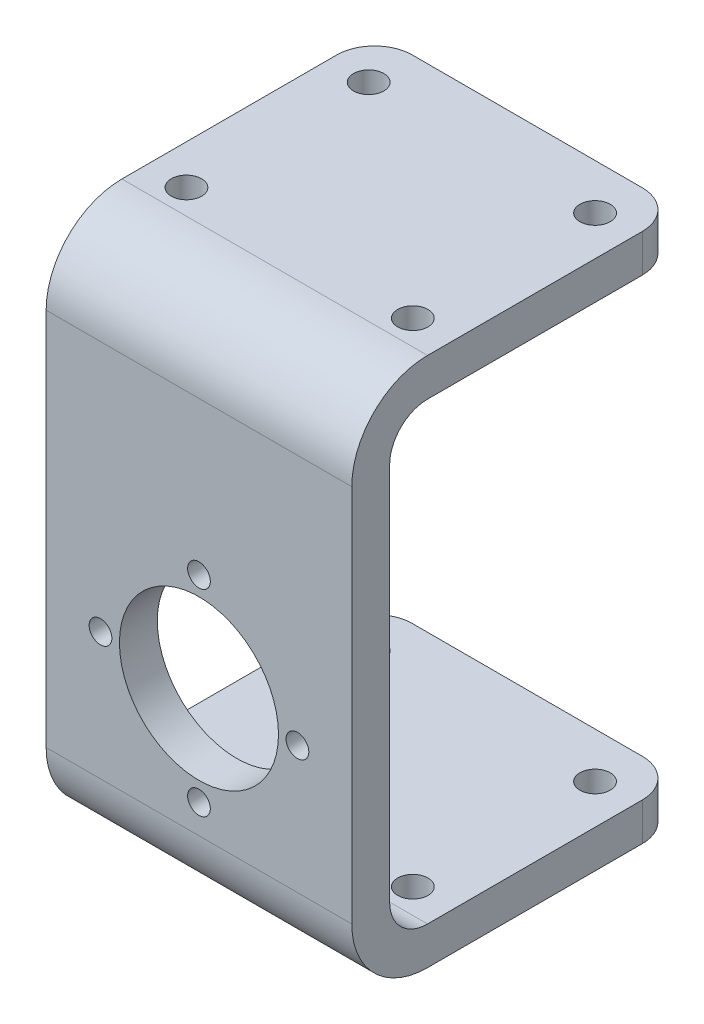
SolidWorks part; units mm, degrees
material "Acrylic"
ref_plane "Front Plane" through (0, 0, 0) normal (0, 0, 1) x (1, 0, 0)
ref_plane "Top Plane" through (0, 0, 0) normal (0, 1, 0) x (1, 0, 0)
ref_plane "Right Plane" through (0, 0, 0) normal (1, 0, 0) x (0, 0, -1)
sketch "Sketch1" plane through (0, 0, 0) normal (0, 1, 0) x (1, 0, 0)
  line L1 (-47.1412, -7.433) -> (-6.7912, -7.433)
  line L2 (-47.1412, -7.433) -> (-47.1412, -50.783)
  line L3 (-47.1412, -50.783) -> (-6.7912, -50.783)
  line L4 (-6.7912, -7.433) -> (-6.7912, -50.783)
extrude "Boss-Extrude1" add sketch "Sketch1" along normal blind 47
sketch "Sketch3" plane through (0, 0, 50.783) normal (0, 0, 1) x (1, 0, 0)
  line L6 (-47.1412, 26.825) -> (-47.1412, 47)
  line L7 (-47.1412, 47) -> (-6.7912, 47)
  line L8 (-6.7912, 26.825) -> (-6.7912, 47)
  arc A1 (-6.7912, 26.825) -> (-47.1412, 26.825) centre (-26.9662, 26.825) ccw
  line M2 (-6.7912, 0) -> (-6.7912, 47)
  line M3 (-6.7912, 47) -> (-47.1412, 47)
  line M4 (-47.1412, 47) -> (-47.1412, 0)
extrude "Cut-Extrude2" cut sketch "Sketch3" against normal blind 102 contours A1 L7 M4 | A1 M2 M3 region at (-11.2977, 42.4936, 50.783) region at (-42.6348, 42.4936, 50.783)
fillet "Fillet1" radius 10 1 edges at (-26.9662, 0, 50.783)
sketch "Sketch5" plane through (-47.1412, 0, 0) normal (-1, 0, 0) x (0, 0, 1)
  line L0 (7.433, 0) -> (-6.6658, 0)
  line L1 (-6.6658, 0) -> (-6.6658, 5)
  line L2 (50.783, 47) -> (50.783, 59.7784)
  line L3 (50.783, 59.7784) -> (45.783, 59.7784)
  line L5 (-6.6658, 5) -> (36.5956, 5)
  line L6 (-6.6658, 5) -> (-6.6658, 59.7784)
  line L7 (-6.6658, 59.7784) -> (45.783, 59.7784)
  line L8 (45.783, 17.5785) -> (45.783, 59.7784)
  line L9 (36.5956, 5) -> (40.783, 5)
  line L12 (45.783, 10) -> (45.783, 17.5785)
  arc A1 (40.783, 5) -> (45.783, 10) centre (40.783, 10) ccw
  line M2 (50.783, 26.825) -> (7.433, 26.825)
  line M3 (7.433, 26.825) -> (7.433, 0)
  dimension "D1" = 5
  dimension "D2" = 5
extrude "Cut-Extrude3" cut sketch "Sketch5" against normal blind 102 contours L8 L7 L6 L5 M2 M3 | L5 L8 M2 M3 region at (-47.1412, 15.9757, 26.4915) region at (-47.1412, 39.1625, 16.6608)
fillet "Fillet2" radius 5 2 edges at (-6.7912, 2.5, 7.433) (-47.1412, 2.5, 7.433)
sketch "Sketch7" plane through (0, 0, 50.783) normal (0, 0, 1) x (1, 0, 0)
  circle A0 centre (-26.9662, 26.825) radius 10.5
  circle A1 centre (-26.9662, 26.825) radius 13
  circle A2 centre (-26.9662, 39.825) radius 1.5
  circle A3 centre (-13.9662, 26.825) radius 1.5
  circle A4 centre (-26.9662, 13.825) radius 1.5
  circle A5 centre (-39.9662, 26.825) radius 1.5
  point P15 (-26.9662, 26.825)
  dimension "D1" = 21
  dimension "D2" = 26
  dimension "D3" = 3
  dimension "D4" = 4
extrude "Cut-Extrude5" cut sketch "Sketch7" against normal blind 10 contours A0 | A1 A2 | A1 A2 | A1 A3 | A1 A3 | A1 A5 | A1 A5 | A1 A4 | A1 A4 region at (-26.9662, 26.825, 50.783) region at (-14.6182, 26.825, 50.783) region at (-13.3454, 26.825, 50.783) region at (-26.9662, 39.173, 50.783) region at (-26.9662, 40.4458, 50.783) region at (-26.9662, 13.2042, 50.783) region at (-26.9662, 14.477, 50.783) region at (-39.3143, 26.825, 50.783) region at (-40.587, 26.825, 50.783)
sketch "Sketch8" plane through (0, 0, 45.783) normal (0, 0, -1) x (-1, 0, 0)
  line L1 (6.7912, 26.825) -> (47.1412, 26.825)
  line L2 (6.7912, 26.825) -> (6.7912, 70)
  line L3 (6.7912, 70) -> (47.1412, 70)
  line L4 (47.1412, 26.825) -> (47.1412, 70)
  line L5 (6.7912, 26.825) -> (47.1412, 70) construction
  line L6 (6.7912, 70) -> (47.1412, 26.825) construction
  point P4 (26.9662, 48.4125)
  dimension "D1" = 40.35
  dimension "D2" = 43.175
extrude "Boss-Extrude2" add sketch "Sketch8" along normal up to surface (38.35 mm away) and the other way blind 5 up to face at (-26.9662, 2.5, 7.433)
sketch "Sketch6" plane through (0, 5, 0) normal (0, 1, 0) x (1, 0, 0)
  line L0 (-27.9141, -7.433) -> (-27.9141, -11.433)
  line L1 (-42.1412, -7.433) -> (-11.7912, -7.433) construction
  line L2 (-47.1412, -24.2783) -> (-43.9112, -24.2783)
  line L3 (-47.1412, -12.433) -> (-47.1412, -40.783) construction
  line L4 (-6.7912, -25.5422) -> (-10.0212, -25.5422)
  line L5 (-6.7912, -12.433) -> (-6.7912, -40.783) construction
  line L6 (-43.9112, -24.2783) -> (-43.9112, -11.433)
  line L7 (-43.9112, -11.433) -> (-10.0212, -11.433)
  line L8 (-10.0212, -11.433) -> (-10.0212, -40.433)
  line L9 (-10.0212, -40.433) -> (-43.9112, -40.433)
  line L10 (-43.9112, -40.433) -> (-43.9112, -24.2783)
  line L11 (-41.9112, -15.433) -> (-41.9112, -37.493)
  line L12 (-12.0212, -15.433) -> (-12.0212, -37.493)
  line L13 (-39.9112, -13.433) -> (-14.0212, -13.433)
  line L14 (-41.9112, -37.493) -> (-12.0212, -37.493)
  circle A0 centre (-41.9112, -13.433) radius 2
  circle A1 centre (-12.0212, -13.433) radius 2
  circle A2 centre (-41.9112, -37.493) radius 2
  circle A3 centre (-12.0212, -37.493) radius 2
  line M12 (-47.1412, -40.783) -> (-6.7912, -40.783)
  dimension "D1" = 4
  dimension "D4" = 4
  dimension "D2" = 24.06
  dimension "D3" = 29
  dimension "D5" = 24.06
  dimension "D6" = 29.89
  dimension "D7" = 29.89
extrude "Cut-Extrude4" cut sketch "Sketch6" against normal blind 102 and the other way blind 102 contours A3 M12 | A3 M12 | A2 M12 | A2 M12 | A1 | A0 region at (-41.9112, 5, 13.433) region at (-42.1942, 5, 37.776) region at (-41.0624, 5, 36.6442) region at (-12.87, 5, 36.6442) region at (-11.7383, 5, 37.776) region at (-12.0212, 5, 13.433)
sketch "Sketch9" plane through (-6.7912, 0, 0) normal (1, 0, 0) x (0, 0, -1)
  line L0 (-7.433, 70) -> (-7.433, 65)
  line L1 (-7.433, 26.825) -> (-7.433, 70) construction
  line L2 (-7.433, 65) -> (-40.7778, 65)
  line L3 (-45.783, 26.825) -> (-45.783, 59.9996)
  line L4 (-45.783, 26.825) -> (-50.783, 26.825)
  line L5 (-50.783, 70) -> (-50.783, 10) construction
  line L6 (-50.783, 26.825) -> (-50.783, 59.9972)
  line L7 (-7.433, 70) -> (-40.7802, 70)
  line L8 (-50.783, 70) -> (-7.433, 70) construction
  line L9 (-7.433, 65) -> (-7.433, 26.825)
  line L10 (-7.433, 26.825) -> (-45.783, 26.825)
  line L11 (-40.7802, 70) -> (-50.783, 70)
  line L12 (-50.783, 70) -> (-50.783, 59.9972)
  arc A0 (-40.7778, 65) -> (-45.783, 59.9996) centre (-40.7778, 59.9948) ccw
  arc A1 (-40.7802, 70) -> (-50.783, 59.9972) centre (-40.7802, 59.9972) ccw
  line M14 (-45.783, 26.825) -> (-7.433, 26.825)
  line M15 (-7.433, 26.825) -> (-7.433, 70)
  line M16 (-7.433, 70) -> (-50.783, 70)
  line M17 (-50.783, 70) -> (-50.783, 10)
extrude "Cut-Extrude6" cut sketch "Sketch9" against normal blind 50 contours L2 A0 L3 M14 M15 | A1 M16 M17 region at (-6.7912, 45.8463, 26.5415) region at (-6.7912, 67.7657, 48.5487)
fillet "Fillet3" radius 5 2 edges at (-6.7912, 67.5, 7.433) (-47.1412, 67.5, 7.433)
sketch "Sketch10" plane through (0, 0, 50.783) normal (0, 0, 1) x (1, 0, 0)
  line L0 (-16.4662, 26.825) -> (-37.4662, 26.825) construction
  line L1 (-12.4662, 26.825) -> (-15.4662, 26.825) construction
  circle A0 centre (-26.9662, 26.825) radius 10.5
  circle A1 centre (-13.9662, 26.825) radius 1.5
  circle A2 centre (-26.9662, 13.825) radius 1.5
  circle A3 centre (-39.9662, 26.825) radius 1.5
  circle A4 centre (-26.9662, 39.825) radius 1.5
  point P17 (-26.9662, 26.825)
  dimension "D1" = 4
extrude "Cut-Extrude7" cut sketch "Sketch10" against normal blind 50
ref_axis "Axis1" through (-26.9662, 39.825, 45.783) along (0, 0, 1)
ref_axis "Axis2" through (-39.9662, 26.825, 45.783) along (0, 0, 1)
ref_axis "Axis3" through (-13.9662, 26.825, 45.783) along (0, 0, 1)
ref_axis "Axis4" through (-26.9662, 13.825, 45.783) along (0, 0, 1)
